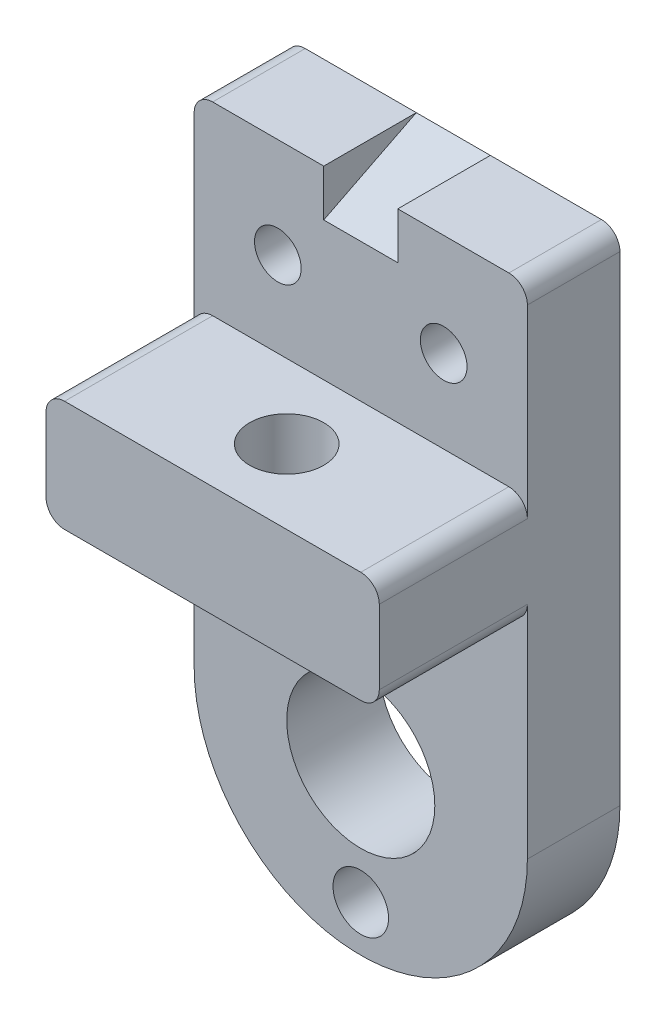
SolidWorks part; units mm, degrees
ref_plane "Alzado" through (0, 0, 0) normal (0, 0, 1) x (1, 0, 0)
ref_plane "Planta" through (0, 0, 0) normal (0, 1, 0) x (1, 0, 0)
ref_plane "Vista lateral" through (0, 0, 0) normal (1, 0, 0) x (0, 0, -1)
sketch "Croquis1" plane through (0, 0, 0) normal (0, 0, 1) x (1, 0, 0)
  line L0 (12.7, 170.942) -> (50.8, 170.942)
  line L1 (-50.8, 170.942) -> (-12.7, 170.942)
  line L2 (-57.15, 164.592) -> (-57.15, 0)
  line L4 (57.15, 164.592) -> (57.15, 0)
  line L5 (-50.8, 69.342) -> (50.8, 69.342)
  line L6 (-57.15, 75.692) -> (-57.15, 101.092)
  line L7 (-50.8, 107.442) -> (50.8, 107.442)
  line L8 (57.15, 75.692) -> (57.15, 101.092)
  line L10 (-12.7, 170.942) -> (-12.7, 154.94)
  line L11 (-12.7, 154.94) -> (12.7, 154.94)
  line L12 (12.7, 170.942) -> (12.7, 154.94)
  arc A0 (-57.15, 0) -> (57.15, 0) centre (0, 0) ccw
  circle A1 centre (0, 0) radius 25.4
  circle A2 centre (-28.702, 41.402) radius 6.35
  circle A3 centre (0, -41.402) radius 9.525
  circle A4 centre (-28.448, 136.652) radius 8.001
  circle A5 centre (28.448, 135.89) radius 8.001
  arc A6 (-57.15, 101.092) -> (-50.8, 107.442) centre (-50.8, 101.092) cw
  arc A7 (-50.8, 69.342) -> (-57.15, 75.692) centre (-50.8, 75.692) cw
  arc A8 (50.8, 69.342) -> (57.15, 75.692) centre (50.8, 75.692) ccw
  arc A9 (50.8, 107.442) -> (57.15, 101.092) centre (50.8, 101.092) cw
  arc A10 (50.8, 170.942) -> (57.15, 164.592) centre (50.8, 164.592) cw
  arc A11 (-50.8, 170.942) -> (-57.15, 164.592) centre (-50.8, 164.592) ccw
  point P27 (-57.15, 69.342)
  point P32 (57.15, 107.442)
  point P35 (57.15, 170.942)
  dimension "D1" = 57.15
  dimension "D5" = 50.8
  dimension "D6" = 19.05
  dimension "D10" = 12.7
  dimension "D15" = 16.002
  dimension "D16" = 16.002
  dimension "D20" = 6.35
  dimension "D21" = 6.35
  dimension "D22" = 6.35
  dimension "D23" = 6.35
  dimension "D24" = 6.35
  dimension "D25" = 6.35
  dimension "D2" = 170.942
  dimension "D3" = 63.5
  dimension "D4" = 38.1
  dimension "D7" = 41.402
  dimension "D8" = 28.702
  dimension "D9" = 95.25
  dimension "D11" = 28.702
  dimension "D12" = 56.896
  dimension "D13" = 41.402
  dimension "D14" = 35.052
  dimension "D17" = 16.002
  dimension "D18" = 25.4
  dimension "D19" = 44.45
extrude "Saliente-Extruir1" add sketch "Croquis1" along normal blind 31.75 contours L2 L7 L4 L1 A5 A4 | L2 A0 L4 L5 A3 A2 A1 region at (0, 137.7071, 0) region at (55.3975, 37.846, 0)
extrude "Saliente-Extruir2" add sketch "Croquis1<3>" along normal blind 82.55 contours L7 L2 L5 L4 region at (0, 88.392, 0)
sketch "Croquis1<3>" plane through (0, 0, 0) normal (0, 0, 1) x (1, 0, 0) same geometry as "Croquis1"
sketch "Croquis3" plane through (0, 107.442, 0) normal (0, 1, 0) x (1, 0, 0)
  line L0 (57.15, -82.55) -> (57.15, -31.75) construction
  line L1 (-50.8, -31.75) -> (50.8, -31.75) construction
  circle A0 centre (0, -57.15) radius 12.7
  dimension "D3" = 25.4
  dimension "D1" = 57.15
  dimension "D2" = 25.4
extrude "Cortar-Extruir1" cut sketch "Croquis3" against normal up to next
sketch "Croquis4" plane through (12.7, 0, 0) normal (-1, 0, 0) x (0, 0, 1)
  line L0 (31.75, 154.94) -> (0, 170.942)
  line L1 (0, 170.942) -> (0, 154.94)
  line L2 (0, 154.94) -> (31.75, 154.94)
extrude "Saliente-Extruir3" add sketch "Croquis4" along normal up to next
